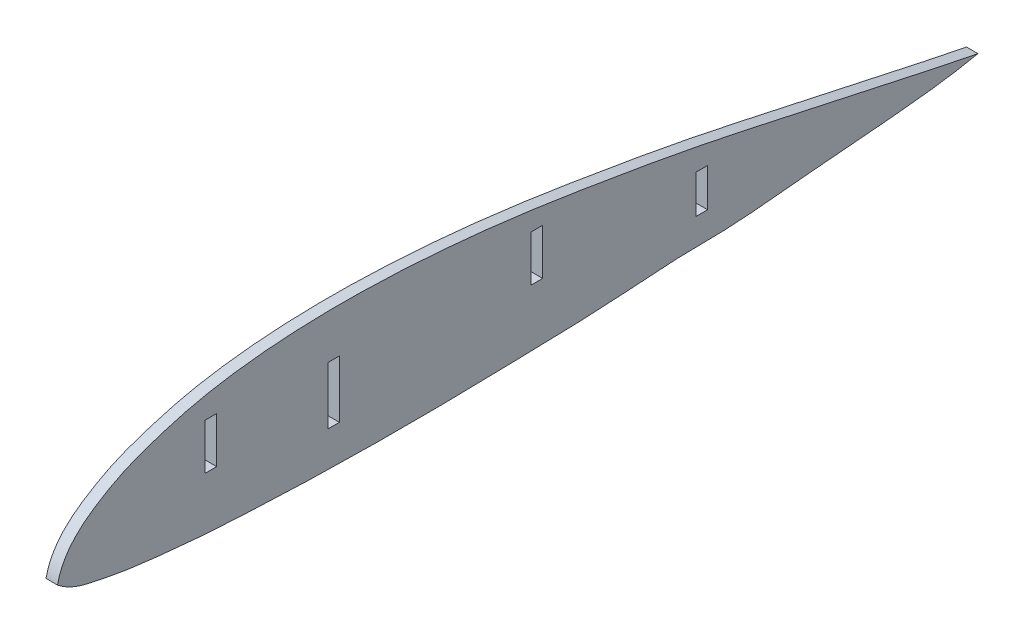
SolidWorks part; units mm, degrees
ref_plane "Спереди" through (0, 0, 0) normal (0, 0, 1) x (1, 0, 0)
ref_plane "Сверху" through (0, 0, 0) normal (0, 1, 0) x (1, 0, 0)
ref_plane "Справа" through (0, 0, 0) normal (1, 0, 0) x (0, 0, -1)
sketch "Эскиз1" plane through (0, 0, 0) normal (1, 0, 0) x (0, 0, -1)
  spline S0 degree 3 poles (-240, 0) (-238.5396, 6.886) (-231.612, 12.3378) (-222.1753, 17.4121) (-214.1119, 20.3435) (-204.1561, 23.2639) (-188.1046, 25.8933) (-168.0072, 26.9601) (-143.9456, 26.0264) (-119.9183, 23.5678) (-95.9538, 19.7588) (-71.9127, 15.562) (-48.006, 10.2206) (-23.9898, 5.1714) (-8.0375, 1.5236) (0, 0) knots 0 0 0 0 0.075346 0.102328 0.12789 0.177564 0.226025 0.321727 0.4173 0.513305 0.60992 0.706974 0.804635 0.902346 1 1 1 1
  spline S1 degree 3 poles (-240, 0) (-236.5239, -2.8866) (-230.2208, -4.0678) (-222.0286, -5.6488) (-214.0096, -6.6085) (-204.0195, -7.6506) (-188.0105, -8.621) (-168.0084, -9.355) (-143.9974, -9.5447) (-119.9964, -9.0006) (-95.9841, -8.4523) (-79.4445, -6.8615) (-63.4129, -6.9414) (-47.4215, -5.1493) (-23.952, -3.3462) (-7.916, -1.6722) (0, 0) knots 0 0 0 0 0.053475 0.078709 0.103753 0.153673 0.203448 0.302856 0.402199 0.501554 0.600955 0.70043 0.70748 0.799996 0.899716 1 1 1 1
  point P0 (-240, 0)
  point P1 (-234, 9.888)
  point P2 (-228, 14.16)
  point P3 (-222, 17.316)
  point P4 (-216, 19.608)
  point P5 (-204, 23.04)
  point P6 (-192, 25.104)
  point P7 (-168, 26.592)
  point P8 (-144, 25.776)
  point P9 (-120, 23.352)
  point P10 (-96, 19.704)
  point P11 (-72, 15.384)
  point P12 (-48, 10.272)
  point P13 (-24, 5.1)
  point P14 (-12, 2.46)
  point P15 (0, 0)
  point P16 (-234, -3.12)
  point P17 (-228, -4.5)
  point P18 (-222, -5.58)
  point P19 (-216, -6.36)
  point P20 (-204, -7.5648)
  point P21 (-192, -8.3472)
  point P22 (-168, -9.24)
  point P23 (-144, -9.4224)
  point P24 (-120, -9)
  point P25 (-96, -8.16)
  point P26 (-72, -6.9024)
  point P27 (-48, -5.34)
  point P28 (-24, -3.24)
  point P29 (-12, -1.98)
extrude "Бобышка-Вытянуть1" add sketch "Эскиз1" along normal blind 3
sketch "Эскиз2" plane through (0, 0, 0) normal (-1, 0, 0) x (0, 0, 1)
  line L13 (169.5, 0) -> (169.5, 15)
  line L14 (169.5, 15) -> (166.5, 15)
  line L15 (166.5, 0) -> (169.5, 0)
  line L16 (166.5, 15) -> (166.5, 0)
  line L17 (70.5, 0) -> (70.5, 10)
  line L18 (70.5, 0) -> (73.5, 0)
  line L19 (70.5, 10) -> (73.5, 10)
  line L20 (73.5, 10) -> (73.5, 0)
  line L21 (201.5, 6) -> (201.5, 18)
  line L22 (201.5, 18) -> (198.5, 18)
  line L23 (113.5, 6) -> (113.5, 18)
  line L24 (201.5, 6) -> (198.5, 6)
  line L25 (198.5, 6) -> (198.5, 18)
  line L26 (116.5, 6) -> (116.5, 18)
  line L27 (116.5, 6) -> (113.5, 6)
  line L28 (116.5, 18) -> (113.5, 18)
  dimension "D1" = 70.5
  dimension "D2" = 10
  dimension "D3" = 113.5
  dimension "D4" = 15
  dimension "D5" = 198.5
  dimension "D6" = 12
  dimension "D7" = 166.5
  dimension "D8" = 12
  dimension "D9" = 6
  dimension "D10" = 6
extrude "Вырез-Вытянуть1" cut sketch "Эскиз2" against normal blind 3
